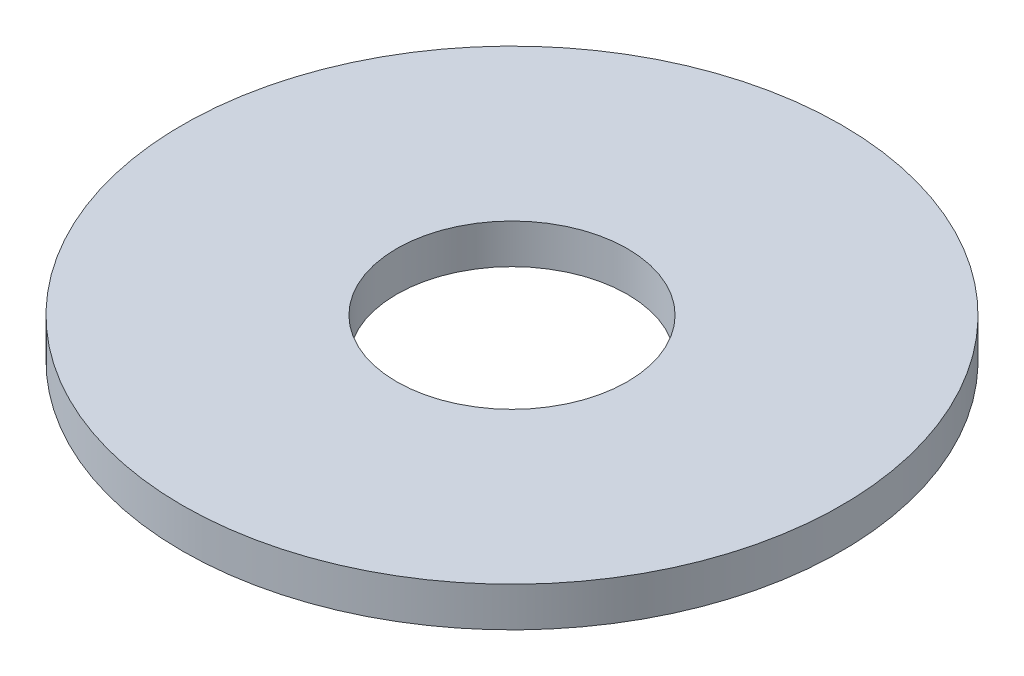
SolidWorks part; units mm, degrees
ref_plane "Front Plane" through (0, 0, 0) normal (0, 0, 1) x (1, 0, 0)
ref_plane "Top Plane" through (0, 0, 0) normal (0, 1, 0) x (1, 0, 0)
ref_plane "Right Plane" through (0, 0, 0) normal (1, 0, 0) x (0, 0, -1)
sketch "Sketch1" plane through (0, 0, 0) normal (0, 1, 0) x (1, 0, 0)
  circle A0 centre (0, 0) radius 100
  dimension "FLANGE_OD" = 200
extrude "Boss-Extrude1" add sketch "Sketch1" along normal blind 12
sketch "Sketch2" plane through (0, 0, 0) normal (0, 1, 0) x (1, 0, 0)
  circle A0 centre (0, 0) radius 35
  dimension "BORE_D" = 70
extrude "Cut-Extrude1" cut sketch "Sketch2" along normal through all
sketch "Sketch3" plane through (0, 12, 0) normal (0, 1, 0) x (1, 0, 0)
  circle A0 centre (0, 0) radius 23.8472 construction
  circle A1 centre (-23.8472, 0) radius 4.1141
  dimension "BOLT_D" = 8.2283
  dimension "BOLT_PCD" = 47.6944
extrude "Cut-Extrude2" cut sketch "Sketch3" against normal blind 7.2418 rebuild error yes
pattern_circular "CirPattern1" count 8 over 360 rebuild error yes
